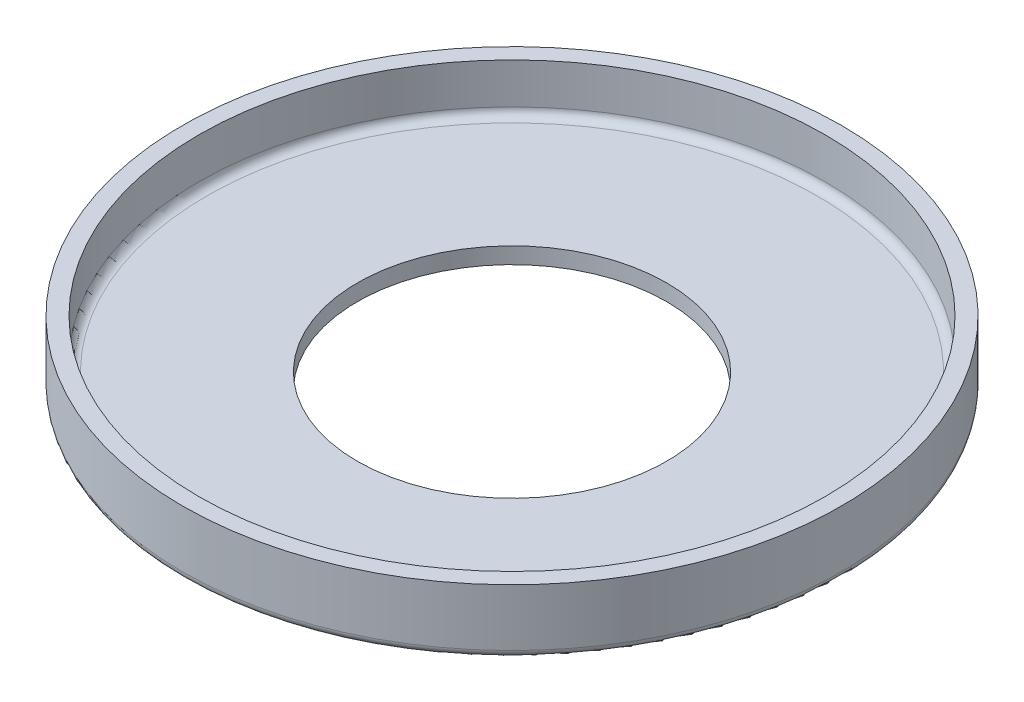
SolidWorks part; units mm, degrees
material "1.0037 (S235JR)"
ref_plane "Front Plane" through (0, 0, 0) normal (0, 0, 1) x (1, 0, 0)
ref_plane "Top Plane" through (0, 0, 0) normal (0, 1, 0) x (1, 0, 0)
ref_plane "Right Plane" through (0, 0, 0) normal (1, 0, 0) x (0, 0, -1)
sketch "Sketch1" plane through (0, 0, 0) normal (0, 1, 0) x (1, 0, 0)
  circle A0 centre (0, 0) radius 19
  circle A1 centre (0, 0) radius 38.5
  circle A2 centre (0, 0) radius 40.5
  dimension "D1" = 38
  dimension "D2" = 77
  dimension "D3" = 2
extrude "Boss-Extrude1" add sketch "Sketch1" along normal blind 2 contours A1 A0 | A2 A1 region at (-37.4111, 0, 0) region at (-39.3545, 0, 0)
extrude "Boss-Extrude2" add sketch "Sketch1<3>" along normal blind 8 contours A2 A1 region at (-39.3545, 0, 0)
sketch "Sketch1<3>" plane through (0, 0, 0) normal (0, 1, 0) x (1, 0, 0) same geometry as "Sketch1"
fillet "Fillet1" radius 1 1 edges at (0, 0, 40.5)
fillet "Fillet2" radius 1 1 edges at (0, 2, 38.5)
